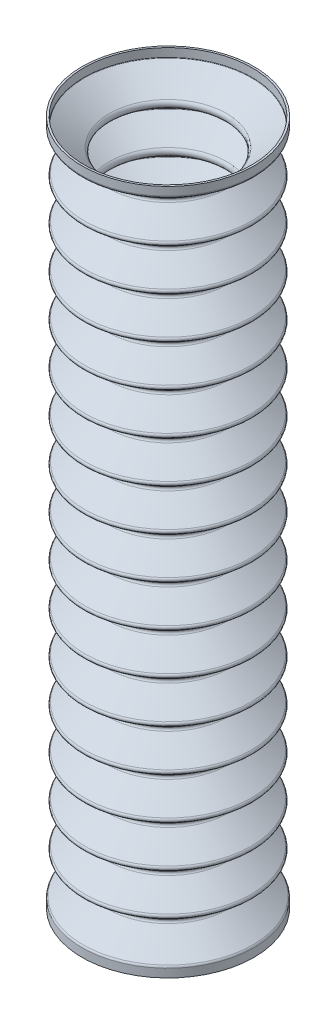
SolidWorks part; units mm, degrees
ref_plane "Front Plane" through (0, 0, 0) normal (0, 0, 1) x (1, 0, 0)
ref_plane "Top Plane" through (0, 0, 0) normal (0, 1, 0) x (1, 0, 0)
ref_plane "Right Plane" through (0, 0, 0) normal (1, 0, 0) x (0, 0, -1)
sketch "Sketch1" plane through (0, 0, 0) normal (0, 0, 1) x (1, 0, 0)
  line L0 (0, 0) -> (0, 422)
  line L1 (0, 0) -> (52.959, 0)
  line L2 (52.959, 0) -> (52.959, 5.1856)
  line L3 (35.052, 0) -> (35.052, 304.8) construction
  line L4 (52.3219, 6.4249) -> (36.7839, 17.5441)
  line L5 (36.7839, 20.0228) -> (51.2271, 30.3585)
  line L6 (35.052, 18.7834) -> (52.959, 18.7834) construction
  line L7 (52.959, 5.969) -> (52.959, 31.5979) construction
  line L8 (51.2271, 32.8372) -> (36.7839, 43.173)
  line L9 (36.7839, 45.6517) -> (51.2271, 55.9874)
  line L10 (51.2271, 58.4661) -> (36.7839, 68.8018)
  line L11 (36.7839, 71.2805) -> (51.2271, 81.6163)
  line L12 (51.2271, 84.095) -> (36.7839, 94.4307)
  line L13 (36.7839, 96.9094) -> (51.2271, 107.2451)
  line L14 (51.2271, 109.7239) -> (36.7839, 120.0596)
  line L15 (36.7839, 122.5383) -> (51.2271, 132.874)
  line L16 (51.2271, 135.3527) -> (36.7839, 145.6885)
  line L17 (36.7839, 148.1672) -> (51.2271, 158.5029)
  line L18 (51.2271, 160.9816) -> (36.7839, 171.3173)
  line L19 (36.7839, 173.796) -> (51.2271, 184.1318)
  line L20 (51.2271, 186.6105) -> (36.7839, 196.9462)
  line L21 (36.7839, 199.4249) -> (51.2271, 209.7606)
  line L22 (51.2271, 212.2394) -> (36.7839, 222.5751)
  line L23 (36.7839, 225.0538) -> (51.2271, 235.3895)
  line L24 (51.2271, 237.8682) -> (36.7839, 248.204)
  line L25 (36.7839, 250.6827) -> (51.2271, 261.0184)
  line L26 (51.2271, 263.4971) -> (36.7839, 273.8328)
  line L27 (36.7839, 276.3115) -> (51.2271, 286.6473)
  line L28 (51.2271, 289.126) -> (36.7839, 299.4617)
  line L29 (36.7839, 301.9404) -> (51.2271, 312.2761)
  line L30 (51.2271, 314.7549) -> (36.7839, 325.0906)
  line L31 (36.7839, 327.5693) -> (51.2271, 337.905)
  line L32 (51.2271, 340.3837) -> (36.7839, 350.7195)
  line L33 (36.7839, 353.1982) -> (51.2271, 363.5339)
  line L34 (51.2271, 366.0126) -> (36.7839, 376.3483)
  line L35 (36.7839, 378.827) -> (51.2271, 389.1628)
  line L36 (51.2271, 391.6415) -> (36.7839, 401.9772)
  line L37 (36.7839, 404.4559) -> (52.3219, 415.5751)
  line L38 (0, 211) -> (155.8281, 211) construction
  line L39 (52.959, 422) -> (52.959, 416.8144)
  line L40 (0, 422) -> (52.959, 422)
  arc A0 (52.959, 5.1856) -> (52.3219, 6.4249) centre (51.435, 5.1856) ccw
  arc A1 (52.959, 416.8144) -> (52.3219, 415.5751) centre (51.435, 416.8144) cw
  arc A2 (36.7839, 401.9772) -> (36.7839, 404.4559) centre (37.6708, 403.2166) cw
  arc A3 (51.2271, 389.1628) -> (51.2271, 391.6415) centre (50.3402, 390.4021) ccw
  arc A4 (36.7839, 376.3483) -> (36.7839, 378.827) centre (37.6708, 377.5877) cw
  arc A5 (51.2271, 363.5339) -> (51.2271, 366.0126) centre (50.3402, 364.7733) ccw
  arc A6 (36.7839, 350.7195) -> (36.7839, 353.1982) centre (37.6708, 351.9588) cw
  arc A7 (51.2271, 337.905) -> (51.2271, 340.3837) centre (50.3402, 339.1444) ccw
  arc A8 (36.7839, 325.0906) -> (36.7839, 327.5693) centre (37.6708, 326.3299) cw
  arc A9 (51.2271, 312.2761) -> (51.2271, 314.7549) centre (50.3402, 313.5155) ccw
  arc A10 (36.7839, 299.4617) -> (36.7839, 301.9404) centre (37.6708, 300.7011) cw
  arc A11 (51.2271, 286.6473) -> (51.2271, 289.126) centre (50.3402, 287.8866) ccw
  arc A12 (36.7839, 273.8328) -> (36.7839, 276.3115) centre (37.6708, 275.0722) cw
  arc A13 (51.2271, 261.0184) -> (51.2271, 263.4971) centre (50.3402, 262.2578) ccw
  arc A14 (36.7839, 248.204) -> (36.7839, 250.6827) centre (37.6708, 249.4433) cw
  arc A15 (51.2271, 235.3895) -> (51.2271, 237.8682) centre (50.3402, 236.6289) ccw
  arc A16 (36.7839, 222.5751) -> (36.7839, 225.0538) centre (37.6708, 223.8144) cw
  arc A17 (51.2271, 209.7606) -> (51.2271, 212.2394) centre (50.3402, 211) ccw
  arc A18 (36.7839, 196.9462) -> (36.7839, 199.4249) centre (37.6708, 198.1856) cw
  arc A19 (51.2271, 184.1318) -> (51.2271, 186.6105) centre (50.3402, 185.3711) ccw
  arc A20 (36.7839, 171.3173) -> (36.7839, 173.796) centre (37.6708, 172.5567) cw
  arc A21 (51.2271, 158.5029) -> (51.2271, 160.9816) centre (50.3402, 159.7423) ccw
  arc A22 (36.7839, 145.6885) -> (36.7839, 148.1672) centre (37.6708, 146.9278) cw
  arc A23 (51.2271, 132.874) -> (51.2271, 135.3527) centre (50.3402, 134.1134) ccw
  arc A24 (36.7839, 120.0596) -> (36.7839, 122.5383) centre (37.6708, 121.2989) cw
  arc A25 (51.2271, 107.2451) -> (51.2271, 109.7239) centre (50.3402, 108.4845) ccw
  arc A26 (36.7839, 94.4307) -> (36.7839, 96.9094) centre (37.6708, 95.6701) cw
  arc A27 (51.2271, 81.6163) -> (51.2271, 84.095) centre (50.3402, 82.8556) ccw
  arc A28 (36.7839, 68.8018) -> (36.7839, 71.2805) centre (37.6708, 70.0412) cw
  arc A29 (51.2271, 55.9874) -> (51.2271, 58.4661) centre (50.3402, 57.2268) ccw
  arc A30 (36.7839, 43.173) -> (36.7839, 45.6517) centre (37.6708, 44.4123) cw
  arc A31 (51.2271, 30.3585) -> (51.2271, 32.8372) centre (50.3402, 31.5979) ccw
  arc A32 (36.7839, 17.5441) -> (36.7839, 20.0228) centre (37.6708, 18.7834) cw
  point P12 (52.959, 18.7834)
  point P37 (52.959, 416.031)
  dimension "D7" = 1.524
  dimension "D1" = 52.959
  dimension "D2" = 5.969
  dimension "D3" = 422
  dimension "D4" = 35.052
  dimension "D6" = 25.6289
  dimension "D5" = 16
revolve "Revolve2" add sketch "Sketch1" angle 360 about L0
shell "Shell1" thickness 1.1938 removed face at (52.959, 0, 0) removed face at (52.959, 422, 0)
ref_axis "Axis1" through (0, 316.992, 0) along (0, -1, 0)
